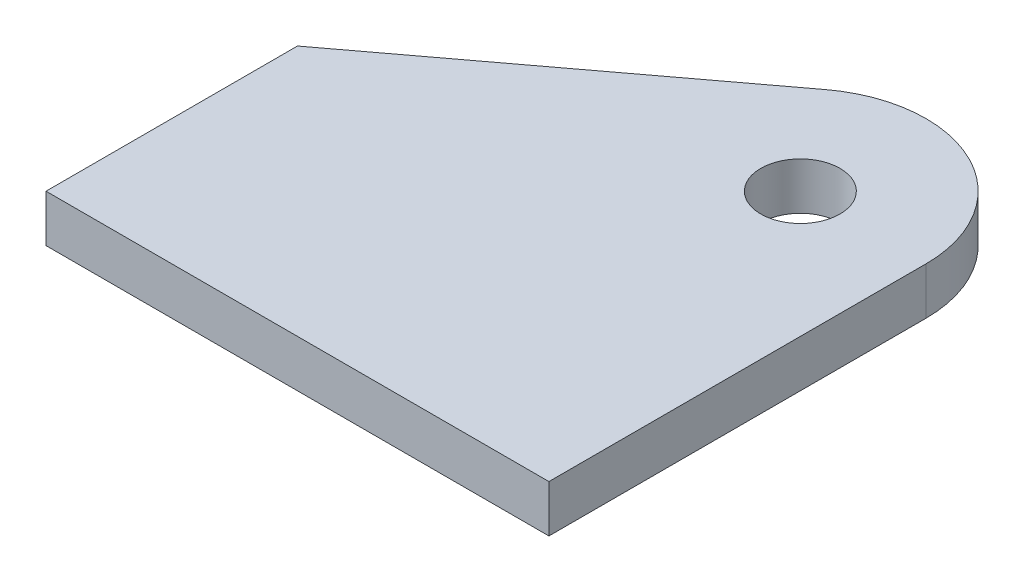
SolidWorks part; units mm, degrees
material "6061 Alloy"
ref_plane "Front Plane" through (0, 0, 0) normal (0, 0, 1) x (1, 0, 0)
ref_plane "Top Plane" through (0, 0, 0) normal (0, 1, 0) x (1, 0, 0)
ref_plane "Right Plane" through (0, 0, 0) normal (1, 0, 0) x (0, 0, -1)
sketch "Sketch1" plane through (0, 0, 0) normal (0, 1, 0) x (1, 0, 0)
  line L0 (0, 0) -> (0, 38.1)
  line L1 (-50.8, 0) -> (-50.8, 25.4)
  line L2 (-50.8, 0) -> (0, 0)
  line L3 (-50.8, 25.4) -> (-20.32, 48.26)
  arc A0 (0, 38.1) -> (-20.32, 48.26) centre (-12.7, 38.1) ccw
  circle A1 centre (-12.7, 38.1) radius 4
  point P10 (-12.7, 37.1354)
  dimension "D1" = 38.1
  dimension "D5" = 8
  dimension "D2" = 12.7
  dimension "D3" = 50.8
  dimension "D4" = 25.4
extrude "Boss-Extrude1" add sketch "Sketch1" along normal blind 4.7625
